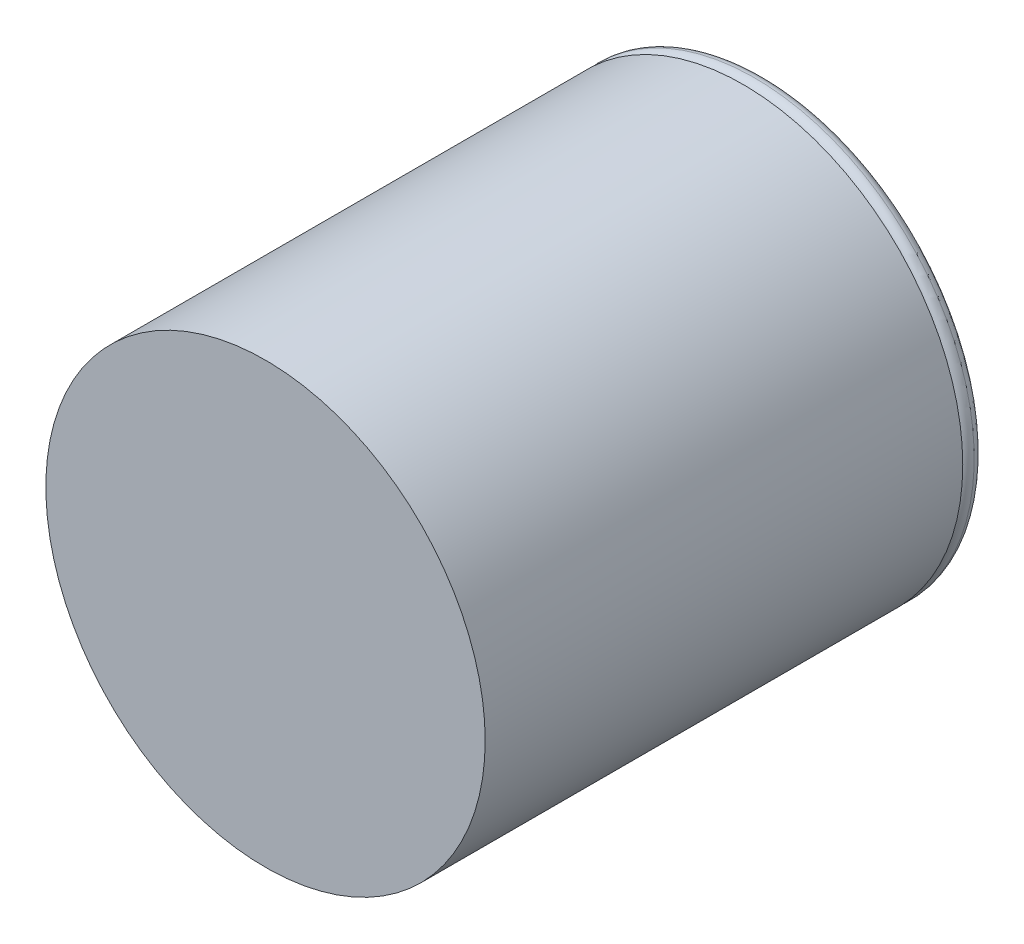
SolidWorks part; units mm, degrees
ref_plane "前视基准面" through (0, 0, 0) normal (0, 0, 1) x (1, 0, 0)
ref_plane "上视基准面" through (0, 0, 0) normal (0, 1, 0) x (1, 0, 0)
ref_plane "右视基准面" through (0, 0, 0) normal (1, 0, 0) x (0, 0, -1)
sketch "草图1" plane through (0, 0, 0) normal (0, 0, 1) x (1, 0, 0)
  circle A0 centre (0, 0) radius 11.5
  dimension "D1" = 23
extrude "凸台-拉伸1" add sketch "草图1" along normal blind 25
sketch "草图2" plane through (0, 0, 0) normal (0, 0, -1) x (-1, 0, 0)
  circle A0 centre (0, 0) radius 7.5
  dimension "D1" = 15
extrude "凸台-拉伸2" add sketch "草图2" along normal blind 0.1
sketch "草图3" plane through (0, 0, -0.1) normal (0, 0, -1) x (-1, 0, 0)
  circle A0 centre (0, 0) radius 11.5
  dimension "D1" = 23
extrude "凸台-拉伸3" add sketch "草图3" along normal blind 1
fillet "圆角1" radius 0.5 1 edges at (-11.5, 0, -1.1)
fillet "圆角2" radius 0.5 2 edges at (-11.5, 0, -0.1) (-7.5, 0, -0.1)
sketch "草图4" plane through (0, 0, -1.1) normal (0, 0, -1) x (-1, 0, 0)
  circle A0 centre (0, 0) radius 2.5
  dimension "D1" = 5
extrude "切除-拉伸1" cut sketch "草图4" against normal blind 0.5
chamfer "倒角1" distance 0.5 angle 45 1 edges at (-2.5, 0, -0.6)
